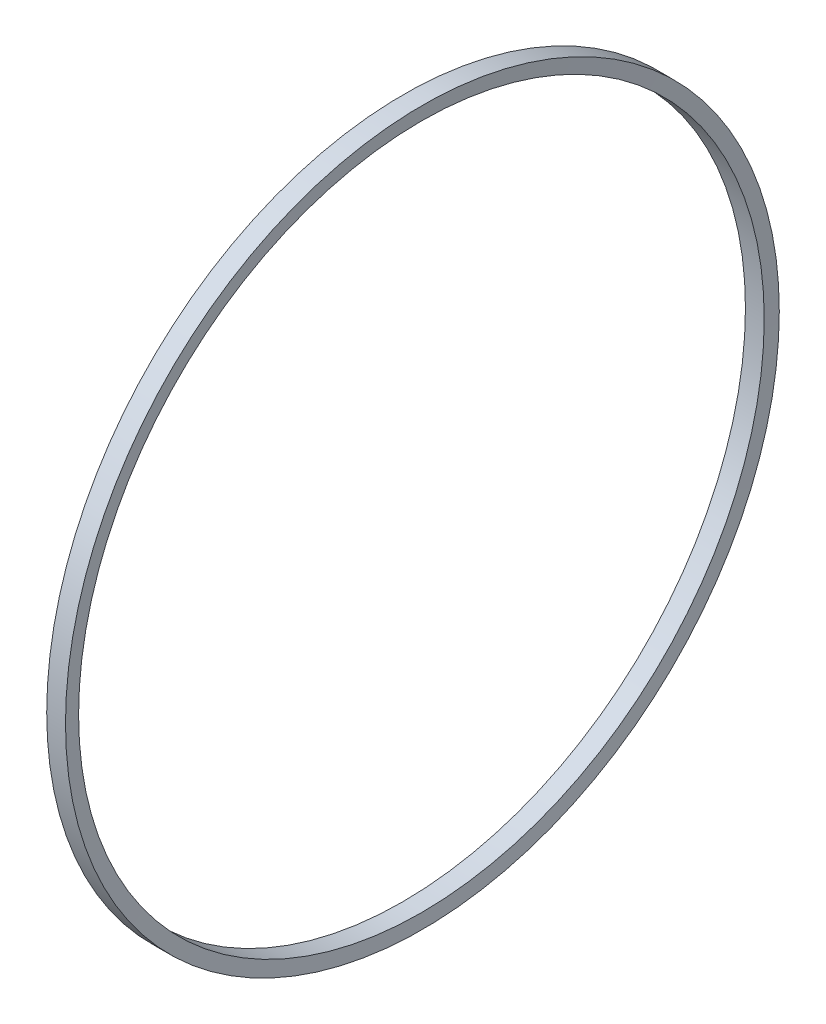
SolidWorks part; units mm, degrees
material "POLYURETHANE (11671)"
ref_plane "Přední rovina" through (0, 0, 0) normal (0, 0, 1) x (1, 0, 0)
ref_plane "Horní rovina" through (0, 0, 0) normal (0, 1, 0) x (1, 0, 0)
ref_plane "Pravá rovina" through (0, 0, 0) normal (1, 0, 0) x (0, 0, -1)
sketch "Skica2" plane through (0, 0, 0) normal (0, 0, 1) x (1, 0, 0)
  line L0 (-15.6789, 38) -> (-17.6789, 38)
  line L1 (-17.6789, 38) -> (-17.7838, 36.5)
  line L2 (-17.7838, 36.5) -> (-15.7838, 36.5)
  line L3 (-15.7838, 36.5) -> (-15.6789, 38)
  line L4 (0, 0) -> (-59.3569, 0) construction
  arc A0 (-15.7133, 37.5) -> (-15.7133, -37.5) centre (509.65, 0) ccw construction
  dimension "D1" = 1.5
  dimension "D2" = 2
  dimension "D3" = 94
  dimension "D4" = 76
revolve "Rotovat1" add sketch "Skica2" angle 360 about L4
